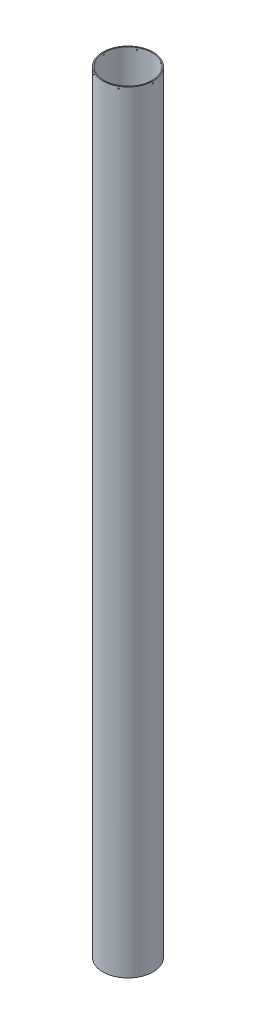
SolidWorks part; units mm, degrees
material "S-Glass Fiber"
ref_plane "Front Plane" through (0, 0, 0) normal (0, 0, 1) x (1, 0, 0)
ref_plane "Top Plane" through (0, 0, 0) normal (0, 1, 0) x (1, 0, 0)
ref_plane "Right Plane" through (0, 0, 0) normal (1, 0, 0) x (0, 0, -1)
sketch "Sketch1" plane through (0, 0, 0) normal (0, 1, 0) x (1, 0, 0)
  circle A0 centre (0, 0) radius 79.375
  circle A1 centre (0, 0) radius 76.2
  dimension "D1" = 152.4
  dimension "D2" = 3.175
extrude "Boss-Extrude1" add sketch "Sketch1" along normal mid plane 2438.4
sketch "Sketch2" plane through (0, 0, 0) normal (1, 0, 0) x (0, 0, -1)
  line L0 (-82.55, 1219.2) -> (82.55, 1219.2) construction
  circle A0 centre (0, 1212.85) radius 1.5875
  dimension "D1" = 3.175
  dimension "D2" = 6.35
extrude "Cut-Extrude1" cut sketch "Sketch2" against normal through all
pattern_circular "CirPattern1" count 6 over 360 about axis through (0, 1219.2, 0) along (0, 1, 0) of "Cut-Extrude1"
